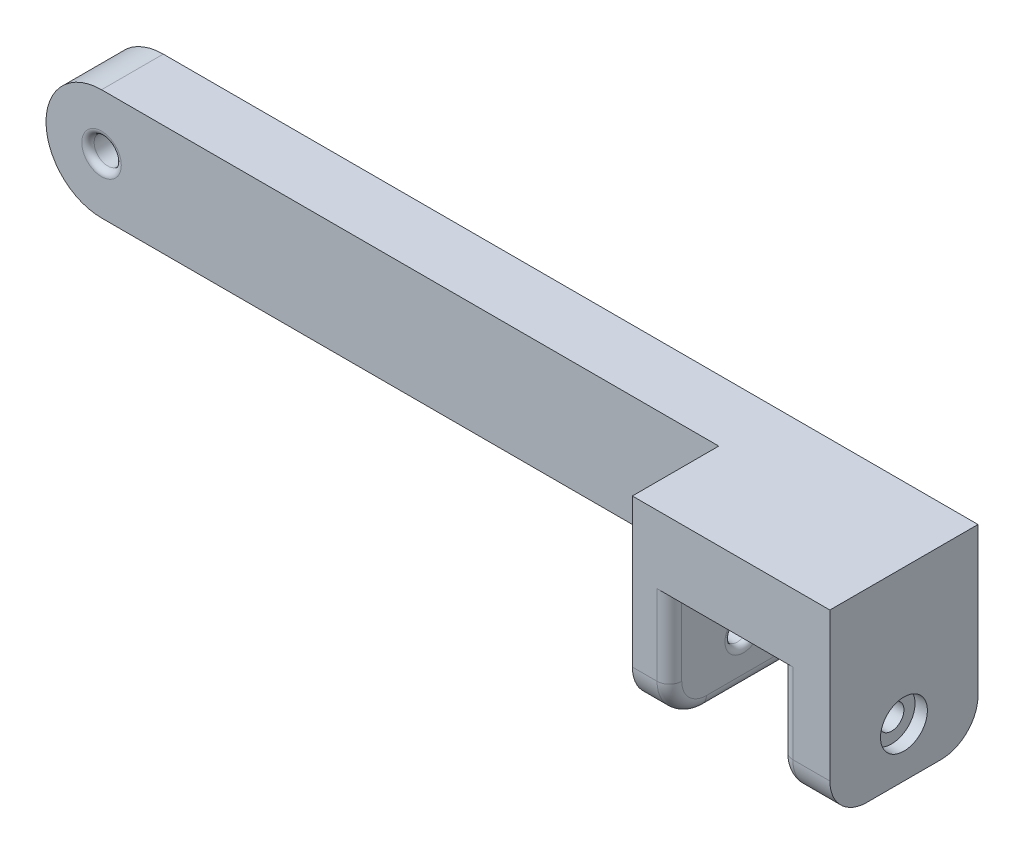
SolidWorks part; units mm, degrees
ref_plane "Front Plane" through (0, 0, 0) normal (0, 0, 1) x (1, 0, 0)
ref_plane "Top Plane" through (0, 0, 0) normal (0, 1, 0) x (1, 0, 0)
ref_plane "Right Plane" through (0, 0, 0) normal (1, 0, 0) x (0, 0, -1)
sketch "Sketch1" plane through (0, 0, 0) normal (0, 0, 1) x (1, 0, 0)
  line L0 (0, 0) -> (50, 0) construction
  line L1 (0, 4.5) -> (50, 4.5)
  line L2 (0, -4.5) -> (50, -4.5)
  line L3 (50, 4.5) -> (50, -4.5)
  circle A0 centre (0, 0) radius 1.1
  circle A2 centre (0, 0) radius 4.5
  dimension "D2" = 9
  dimension "D1" = 50
extrude "Boss-Extrude1" add sketch "Sketch1" along normal blind 5 contours A0 A2 | A2 L0 L1 | L0 A2 L2 region at (26.7563, 0, 0) region at (3.092, 3.092, 0)
sketch "Sketch2" plane through (0, 4.5, 0) normal (0, 1, 0) x (1, 0, 0)
  line L0 (50, -5) -> (50, 0) construction
  line L2 (0, 0) -> (50, 0) construction
  line L3 (50, 0) -> (66, 0)
  line L4 (50, 0) -> (50, -12)
  line L5 (50, -12) -> (66, -12)
  line L6 (66, 0) -> (66, -12)
  line L7 (50, 0) -> (66, -12) construction
  line L8 (50, -12) -> (66, 0) construction
  point P4 (58, -6)
  dimension "D1" = 12
  dimension "D2" = 0
  dimension "D3" = 6
  dimension "D4" = 16
extrude "Boss-Extrude2" add sketch "Sketch2" against normal blind 15
sketch "Sketch3" plane through (0, 4.5, 0) normal (0, 1, 0) x (1, 0, 0)
  line L0 (50, -12) -> (66, -12) construction
  line L1 (53, 3.5) -> (62, 3.5)
  line L2 (53, 3.5) -> (53, -12)
  line L3 (53, -12) -> (62, -12)
  line L4 (62, 3.5) -> (62, -12)
  line L5 (53, 3.5) -> (62, -12) construction
  line L6 (53, -12) -> (62, 3.5) construction
  line L7 (50, -5) -> (50, -12) construction
  point P0 (57.5, -4.25)
  dimension "D1" = 9
  dimension "D2" = 3
extrude "Cut-Extrude1" cut sketch "Sketch3" against normal blind 9.5 from offset 5.5 offset against normal yes
sketch "Sketch4" plane through (66, 0, 0) normal (1, 0, 0) x (0, 0, -1)
  line L0 (-12, -10.5) -> (0, -10.5) construction
  line L2 (0, -10.5) -> (0, 4.5) construction
  circle A0 centre (-6, -6.5) radius 1
  dimension "D1" = 4
  dimension "D2" = 6
extrude "Cut-Extrude2" cut sketch "Sketch4" against normal blind 16
fillet "Fillet2" radius 0.5 1 edges at (53, -6.5, 7)
sketch "Sketch5" plane through (66, 0, 0) normal (1, 0, 0) x (0, 0, -1)
  circle A0 centre (-6, -6.5) radius 1.9
extrude "Cut-Extrude3" cut sketch "Sketch5" against normal blind 1 contours A0
fillet "Fillet3" radius 1 6 edges at (53, -10.5, 6) (53, -5.75, 12) (53, -5.75, 0) (62, -5.75, 12) (62, -5.75, 0) (62, -10.5, 6)
sketch "Sketch6" plane through (50, 0, 0) normal (-1, 0, 0) x (0, 0, 1)
  circle A0 centre (6, -6.5) radius 2
extrude "Cut-Extrude4" cut sketch "Sketch6" along normal blind 5.5 from offset 0.5 offset against normal yes
fillet "Fillet4" radius 3 8 edges at (52.7071, -10.2071, 0.2929) (52.7071, -10.2071, 11.7071) (62.2929, -10.2071, 11.7071) (62.2929, -10.2071, 0.2929) (64.5, -10.5, 0) (64.5, -10.5, 12) (51, -10.5, 12) (51, -10.5, 0)
fillet "Fillet5" radius 0.5 2 edges at (1.1, 0, 5) (1.1, 0, 0)
